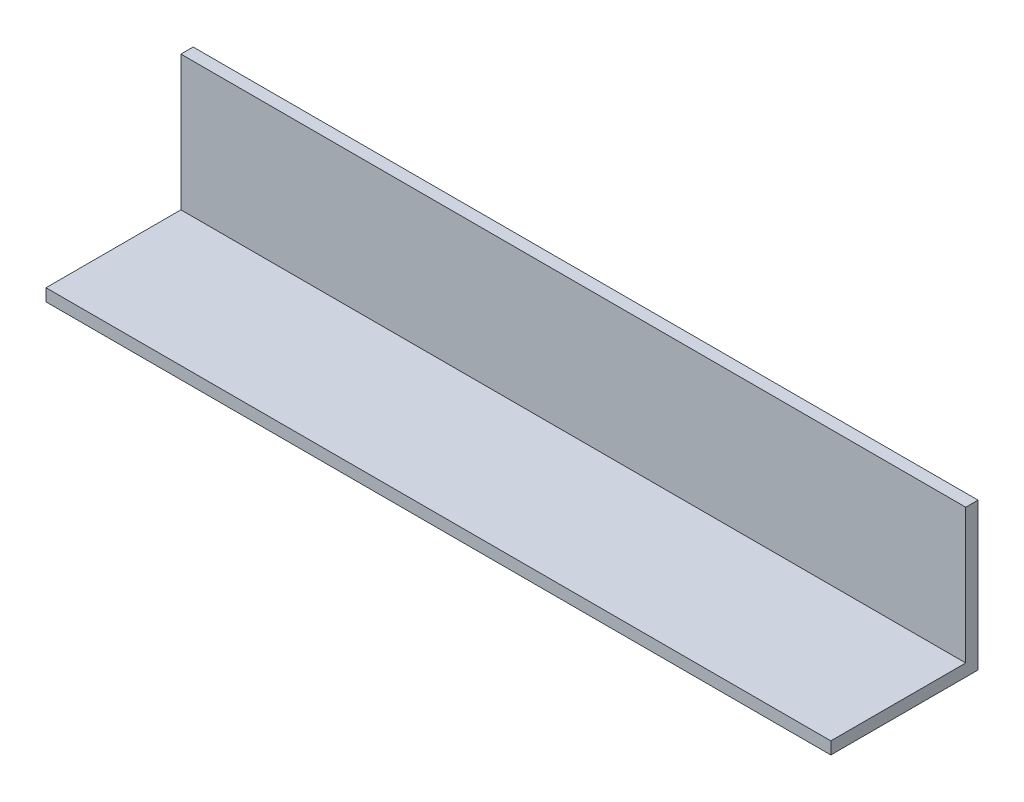
SolidWorks part; units mm, degrees
ref_plane "Front Plane" through (0, 0, 0) normal (0, 0, 1) x (1, 0, 0)
ref_plane "Top Plane" through (0, 0, 0) normal (0, 1, 0) x (1, 0, 0)
ref_plane "Right Plane" through (0, 0, 0) normal (1, 0, 0) x (0, 0, -1)
sketch "Sketch2" plane through (0, 0, 0) normal (1, 0, 0) x (0, 0, -1)
  line L1 (0, 0) -> (76.2, 0)
  line L2 (0, 0) -> (0, 76.2)
  line L3 (0, 76.2) -> (76.2, 76.2)
  line L4 (76.2, 0) -> (76.2, 76.2)
  line L5 (0, 76.2) -> (69.85, 76.2)
  line L6 (0, 76.2) -> (0, 6.35)
  line L7 (0, 6.35) -> (69.85, 6.35)
  line L8 (69.85, 76.2) -> (69.85, 6.35)
  dimension "D1" = 76.2
  dimension "D2" = 76.2
  dimension "D3" = 6.35
  dimension "D4" = 6.35
extrude "Boss-Extrude2" add sketch "Sketch2" along normal blind 406.4 contours L3 L8 L7 L2 L1 L4 region at (0, 3.175, -1.0776)
